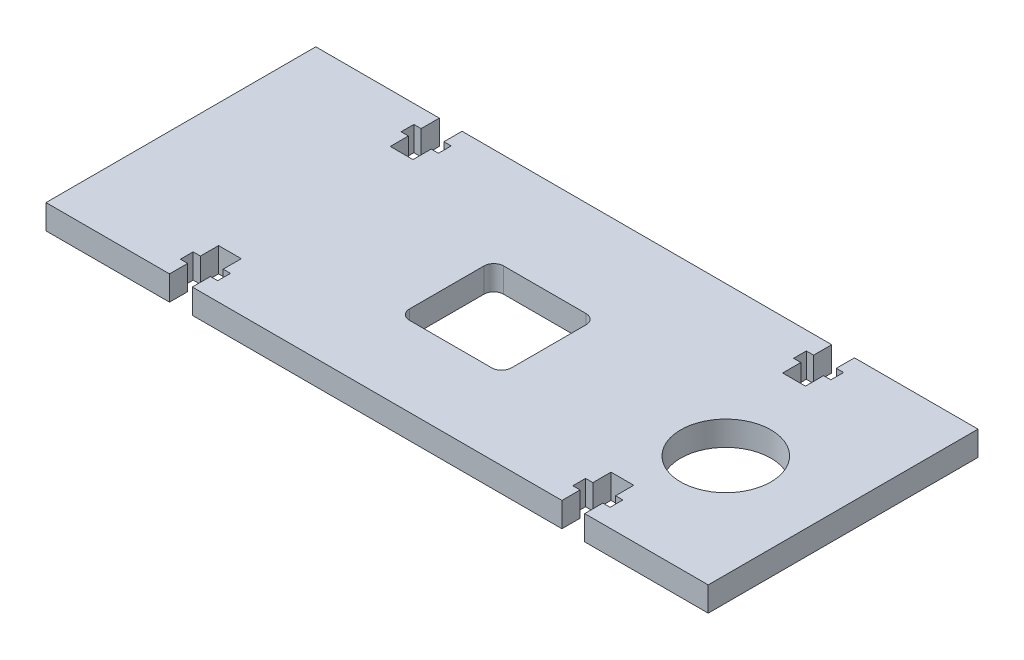
SolidWorks part; units mm, degrees
ref_plane "Front Plane" through (0, 0, 0) normal (0, 0, 1) x (1, 0, 0)
ref_plane "Top Plane" through (0, 0, 0) normal (0, 1, 0) x (1, 0, 0)
ref_plane "Right Plane" through (0, 0, 0) normal (1, 0, 0) x (0, 0, -1)
sketch "Sketch1" plane through (0, 0, 0) normal (0, 1, 0) x (1, 0, 0)
  line L1 (-42.8625, -17.4625) -> (42.8625, -17.4625)
  line L2 (-42.8625, -17.4625) -> (-42.8625, 17.4625)
  line L3 (-42.8625, 17.4625) -> (42.8625, 17.4625)
  line L4 (42.8625, -17.4625) -> (42.8625, 17.4625)
  line L5 (-42.8625, -17.4625) -> (42.8625, 17.4625) construction
  line L6 (-42.8625, 17.4625) -> (42.8625, -17.4625) construction
  point P0 (0, 0)
  dimension "D1" = 85.725
  dimension "D2" = 34.925
extrude "Boss-Extrude1" add sketch "Sketch1" along normal blind 3.175
sketch "Sketch2" plane through (0, 0, 0) normal (0, -1, 0) x (-1, 0, 0)
  line L0 (3.3881, -2.4141) -> (-1.7731, 0.3271) construction
  line L2 (7.4115, 5.0525) -> (-5.7965, 5.0525)
  line L3 (7.4115, 5.0525) -> (7.4115, -7.1395)
  line L4 (7.4115, -7.1395) -> (-5.7965, -7.1395)
  line L5 (-5.7965, 5.0525) -> (-5.7965, -7.1395)
  line L6 (7.4115, 5.0525) -> (-5.7965, -7.1395) construction
  line L7 (7.4115, -7.1395) -> (-5.7965, 5.0525) construction
  circle A0 centre (-29.5375, -1.8635) radius 5.842
  point P4 (0.8075, -1.0435)
  dimension "D3" = 11.684
  dimension "D1" = 13.208
  dimension "D2" = 12.192
extrude "Cut-Extrude1" cut sketch "Sketch2" against normal through all
fillet "Fillet1" radius 1.27 4 edges at (5.7965, 1.5875, -5.0525) (-7.4115, 1.5875, -5.0525) (5.7965, 1.5875, 7.1395) (-7.4115, 1.5875, 7.1395)
sketch "Sketch3" plane through (0, 0, 0) normal (0, -1, 0) x (1, 0, 0)
  line L0 (-42.8625, 17.4625) -> (42.8625, 17.4625) construction
  line L1 (-26.8732, 17.4625) -> (-23.9268, 17.4625)
  line L2 (-26.8732, 17.4625) -> (-26.8732, 15.113)
  line L3 (-26.8732, 11.1125) -> (-23.9268, 11.1125)
  line L4 (-23.9268, 17.4625) -> (-23.9268, 15.113)
  line L5 (-26.8732, 17.4625) -> (-23.9268, 11.1125) construction
  line L6 (-26.8732, 15.113) -> (-27.813, 15.113)
  line L7 (-22.987, 13.462) -> (-23.9268, 13.462)
  line L8 (-22.987, 13.462) -> (-22.987, 15.113)
  line L9 (-22.987, 15.113) -> (-23.9268, 15.113)
  line L10 (-27.813, 13.462) -> (-27.813, 15.113)
  line L11 (-22.987, 13.462) -> (-27.813, 15.113) construction
  line L12 (-22.987, 15.113) -> (-27.813, 13.462) construction
  line L13 (-23.9268, 13.462) -> (-23.9268, 11.1125)
  line L14 (-26.8732, 13.462) -> (-27.813, 13.462)
  line L15 (-26.8732, 13.462) -> (-26.8732, 11.1125)
  line L16 (-25.4, 11.1125) -> (-25.4, 17.4625) construction
  line L17 (0, 17.4625) -> (0, -17.4625) construction
  line L18 (42.8625, -17.4625) -> (-42.8625, -17.4625) construction
  line L19 (25.4, 11.1125) -> (25.4, 17.4625) construction
  line L20 (22.987, 15.113) -> (27.813, 13.462) construction
  line L21 (22.987, 13.462) -> (27.813, 15.113) construction
  line L22 (26.8732, 17.4625) -> (23.9268, 11.1125) construction
  line L23 (26.8732, 13.462) -> (26.8732, 11.1125)
  line L24 (26.8732, 13.462) -> (27.813, 13.462)
  line L25 (23.9268, 13.462) -> (23.9268, 11.1125)
  line L26 (27.813, 13.462) -> (27.813, 15.113)
  line L27 (22.987, 15.113) -> (23.9268, 15.113)
  line L28 (22.987, 13.462) -> (22.987, 15.113)
  line L29 (22.987, 13.462) -> (23.9268, 13.462)
  line L30 (26.8732, 15.113) -> (27.813, 15.113)
  line L31 (23.9268, 17.4625) -> (23.9268, 15.113)
  line L32 (26.8732, 11.1125) -> (23.9268, 11.1125)
  line L33 (26.8732, 17.4625) -> (26.8732, 15.113)
  line L34 (26.8732, 17.4625) -> (23.9268, 17.4625)
  line L35 (-42.8625, 0) -> (-37.7203, 0) construction
  line L36 (-42.8625, -17.4625) -> (-42.8625, 17.4625) construction
  line L37 (26.8732, -17.4625) -> (23.9268, -11.1125) construction
  line L38 (22.987, -13.462) -> (27.813, -15.113) construction
  line L39 (22.987, -15.113) -> (27.813, -13.462) construction
  line L40 (25.4, -11.1125) -> (25.4, -17.4625) construction
  line L41 (26.8732, -17.4625) -> (23.9268, -17.4625)
  line L42 (26.8732, -17.4625) -> (26.8732, -15.113)
  line L43 (26.8732, -11.1125) -> (23.9268, -11.1125)
  line L44 (23.9268, -17.4625) -> (23.9268, -15.113)
  line L45 (26.8732, -15.113) -> (27.813, -15.113)
  line L46 (22.987, -13.462) -> (23.9268, -13.462)
  line L47 (22.987, -13.462) -> (22.987, -15.113)
  line L48 (22.987, -15.113) -> (23.9268, -15.113)
  line L49 (27.813, -13.462) -> (27.813, -15.113)
  line L50 (23.9268, -13.462) -> (23.9268, -11.1125)
  line L51 (26.8732, -13.462) -> (27.813, -13.462)
  line L52 (26.8732, -13.462) -> (26.8732, -11.1125)
  line L53 (-25.4, -11.1125) -> (-25.4, -17.4625) construction
  line L54 (-22.987, -15.113) -> (-27.813, -13.462) construction
  line L55 (-22.987, -13.462) -> (-27.813, -15.113) construction
  line L56 (-26.8732, -17.4625) -> (-23.9268, -11.1125) construction
  line L57 (-26.8732, -13.462) -> (-26.8732, -11.1125)
  line L58 (-26.8732, -13.462) -> (-27.813, -13.462)
  line L59 (-23.9268, -13.462) -> (-23.9268, -11.1125)
  line L60 (-27.813, -13.462) -> (-27.813, -15.113)
  line L61 (-22.987, -15.113) -> (-23.9268, -15.113)
  line L62 (-22.987, -13.462) -> (-22.987, -15.113)
  line L63 (-22.987, -13.462) -> (-23.9268, -13.462)
  line L64 (-26.8732, -15.113) -> (-27.813, -15.113)
  line L65 (-23.9268, -17.4625) -> (-23.9268, -15.113)
  line L66 (-26.8732, -11.1125) -> (-23.9268, -11.1125)
  line L67 (-26.8732, -17.4625) -> (-26.8732, -15.113)
  line L68 (-26.8732, -17.4625) -> (-23.9268, -17.4625)
  point P6 (-25.4, 14.2875)
  point P18 (-25.4, 14.2875)
  point P36 (25.4, 14.2875)
  point P56 (25.4, -14.2875)
  point P71 (-25.4, -14.2875)
  dimension "D1" = 6.35
  dimension "D2" = 2.9464
  dimension "D3" = 1.651
  dimension "D4" = 4.826
  dimension "D5" = 25.4
extrude "Cut-Extrude2" cut sketch "Sketch3" against normal through all
